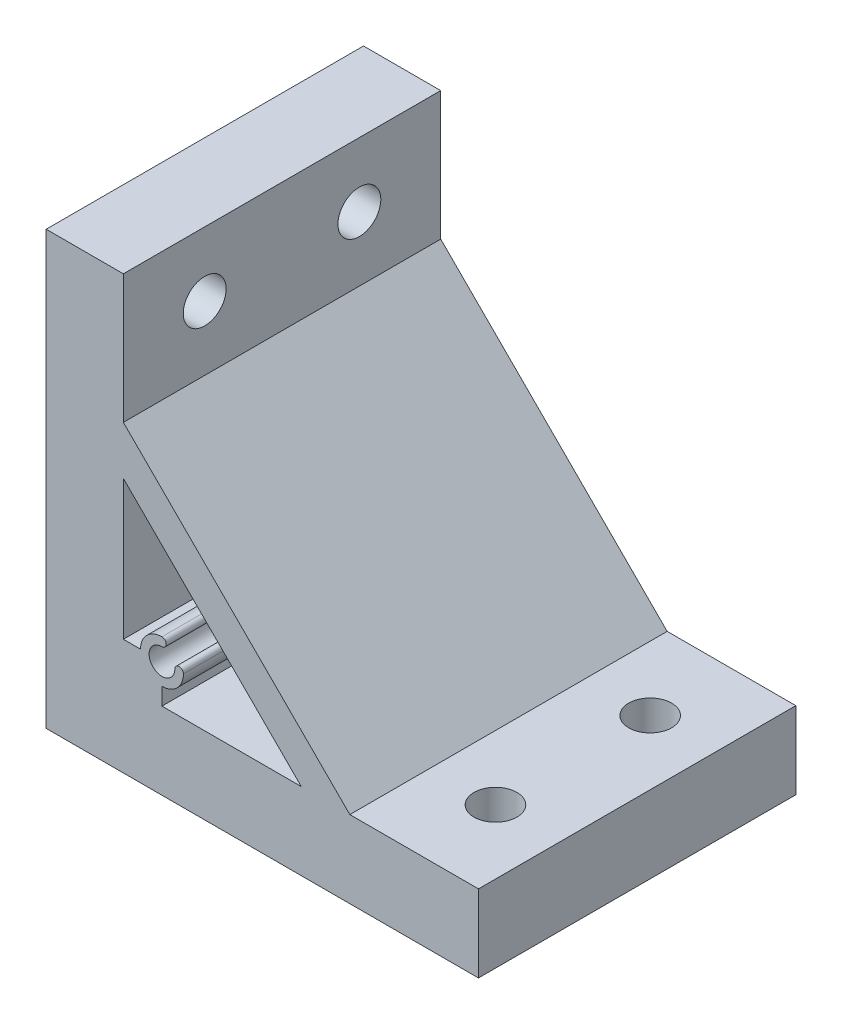
SolidWorks part; units mm, degrees
ref_plane "Front Plane" through (0, 0, 0) normal (0, 0, 1) x (1, 0, 0)
ref_plane "Top Plane" through (0, 0, 0) normal (0, 1, 0) x (1, 0, 0)
ref_plane "Right Plane" through (0, 0, 0) normal (1, 0, 0) x (0, 0, -1)
sketch "Sketch1" plane through (0, 0, 0) normal (0, 0, 1) x (1, 0, 0)
  line L0 (0, 0) -> (0, 50.402)
  line L1 (0, 0) -> (50.402, 0)
  line L2 (50.402, 0) -> (50.402, 9)
  line L3 (50.402, 9) -> (35.402, 9)
  line L4 (0, 50.402) -> (9, 50.402)
  line L5 (9, 50.402) -> (9, 35.402)
  line L7 (9, 29.7451) -> (29.7451, 9)
  line L8 (9, 35.402) -> (35.402, 9)
  line L9 (9, 29.7451) -> (9, 13.5)
  line L10 (9, 13.5) -> (11, 13.5)
  line L11 (29.7451, 9) -> (13.5, 9)
  line L12 (13.5, 9) -> (13.5, 11)
  line L13 (0, 0) -> (22.201, 22.201) construction
  line L14 (13.5, 15) -> (13.5, 16)
  line L15 (15, 13.5) -> (16, 13.5)
  arc A0 (13.5, 16) -> (16, 13.5) centre (13.5, 13.5) ccw
  arc A1 (13.5, 15) -> (15, 13.5) centre (13.5, 13.5) ccw
  circle A2 centre (13.5, 15.5) radius 0.5
  circle A3 centre (15.5, 13.5) radius 0.5
  dimension "D7" = 5
  dimension "D8" = 1
  dimension "D1" = 50.402
  dimension "D2" = 9
  dimension "D3" = 15
  dimension "D4" = 4
  dimension "D5" = 2
  dimension "D6" = 2
extrude "Boss-Extrude2" add sketch "Sketch1" along normal blind 37 contours L0 L13 A0 L10 L9 L7 L8 L5 L4 | L13 L1 L2 L3 L8 L7 L11 L12 A0 region at (27.0473, 5.8877, 0) region at (5.8877, 27.0473, 0)
extrude "Boss-Extrude3" add sketch "Sketch1<4>" along normal blind 37 contours L14 A2 | L15 A3 | A1 L15 A0 L14 region at (13.7122, 15.5, 0) region at (15.5, 13.7122, 0)
sketch "Sketch1<4>" plane through (0, 0, 0) normal (0, 0, 1) x (1, 0, 0) same geometry as "Sketch1"
sketch "Sketch2" plane through (9, 0, 0) normal (1, 0, 0) x (0, 0, -1)
  line L0 (-18.5, 50.402) -> (-18.5, 35.402) construction
  line L3 (-27.517, 42.902) -> (-9.483, 42.902)
  line L4 (-37, 50.402) -> (0, 50.402) construction
  line L5 (-37, 35.402) -> (0, 35.402) construction
  circle A0 centre (-27.517, 42.902) radius 2.5
  circle A1 centre (-9.483, 42.902) radius 2.5
  point P10 (-10.2762, 44.425)
  point P11 (-18.5, 42.902)
  dimension "D2" = 5
  dimension "D1" = 18.034
extrude "Cut-Extrude1" cut sketch "Sketch2" against normal up to next contours A0 | A1 region at (9, 45.3313, 9.483) region at (9, 42.902, 29.9463)
ref_plane "Plane1" through (0, 0, 0) normal (0.7071, -0.7071, 0) x (0, 0, -1)
mirror "Mirror1" about plane through (0, 0, 0) normal (0.7071, -0.7071, 0) of "Cut-Extrude1"
